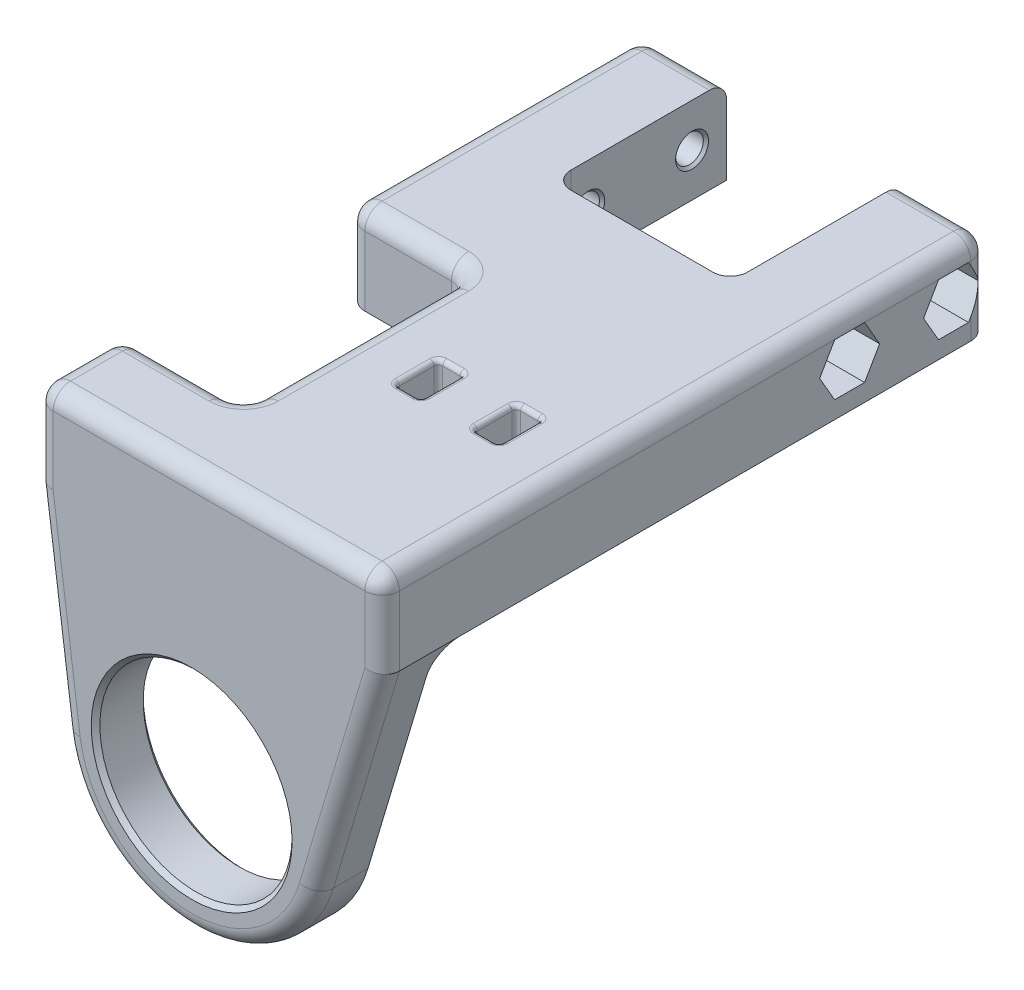
SolidWorks part; units mm, degrees
ref_plane "Top Plane" through (0, 0, 0) normal (0, 0, 1) x (1, 0, 0)
ref_plane "Right Plane" through (0, 0, 0) normal (0, 1, 0) x (1, 0, 0)
ref_plane "Front Plane" through (0, 0, 0) normal (1, 0, 0) x (0, 0, -1)
sketch "Sketch1" plane through (0, 0, 0) normal (0, 0, 1) x (1, 0, 0)
  line L0 (0, 0) -> (0, 31.25) construction
  line L1 (22, 31.25) -> (22, 21.25)
  line L2 (-18, 31.25) -> (22, 31.25)
  line L3 (-18, 31.25) -> (-18, 21.25)
  line L4 (22, 21.25) -> (14.3729, -4.2919)
  line L5 (-18, 21.25) -> (-14.8656, -2.0038)
  line L6 (-18, 21.25) -> (22, 21.25) construction
  arc A0 (-14.8656, -2.0038) -> (14.3729, -4.2919) centre (0, 0) ccw construction
  circle A1 centre (0, 0) radius 11 construction
  circle A2 centre (0, 0) radius 4 construction
  arc A3 (-14.8656, -2.0038) -> (14.3729, -4.2919) centre (0, 0) ccw
  dimension "D1" = 30
  dimension "D2" = 22
  dimension "D3" = 8
  dimension "D6" = 10
  dimension "D4" = 21.25
  dimension "D5" = 40
  dimension "D7" = 18
extrude "Boss-Extrude1" add sketch "Sketch1" along normal blind 6
sketch "Sketch2" plane through (0, 0, 6) normal (0, 0, 1) x (1, 0, 0)
  circle A2 centre (0, 0) radius 11.1
  circle A3 centre (0, 0) radius 11.1
  dimension "D1" = 0.1
extrude "Cut-Extrude1" cut sketch "Sketch2" against normal through all
sketch "Sketch3" plane through (0, 0, 0) normal (0, 0, -1) x (-1, 0, 0)
  line L0 (18, 31.25) -> (-22, 31.25) construction
  line L1 (-22, 31.25) -> (-12, 31.25) construction
  line L2 (-22, 31.25) -> (-22, 21.25) construction
  line L3 (-22, 21.25) -> (-12, 21.25) construction
  line L4 (-12, 31.25) -> (-12, 21.25) construction
  line L5 (8, 31.25) -> (18, 31.25) construction
  line L6 (8, 31.25) -> (8, 21.25) construction
  line L7 (8, 21.25) -> (18, 21.25) construction
  line L8 (18, 31.25) -> (18, 21.25) construction
  line L9 (-12, 26.25) -> (8, 26.25) construction
  line L11 (-2, 26.25) -> (-2, 31.25) construction
  line L13 (-22, 31.25) -> (18, 31.25)
  line L14 (-22, 31.25) -> (-22, 21.25)
  line L15 (-22, 21.25) -> (18, 21.25)
  line L16 (18, 31.25) -> (18, 21.25)
  point P12 (-2, 26.25)
  dimension "D1" = 20
extrude "Boss-Extrude2" add sketch "Sketch3" along normal blind 44
sketch "Sketch4" plane through (0, 0, -44) normal (0, 0, -1) x (-1, 0, 0)
  line L0 (-22, 21.25) -> (18, 21.25) construction
  line L1 (-22, 31.25) -> (-12.2, 31.25)
  line L2 (-22, 31.25) -> (-22, 21.25)
  line L3 (-22, 21.25) -> (-12.2, 21.25)
  line L4 (-12.2, 31.25) -> (-12.2, 21.25)
  line L5 (8.2, 31.25) -> (18, 31.25)
  line L6 (8.2, 31.25) -> (8.2, 21.25)
  line L7 (8.2, 21.25) -> (18, 21.25)
  line L8 (18, 31.25) -> (18, 21.25)
  line L9 (-12, 31.25) -> (-12, 21.25) construction
  line L10 (8, 31.25) -> (8, 21.25) construction
  line L11 (18, 31.25) -> (-22, 31.25) construction
  dimension "D1" = 0.2
  dimension "D2" = 0.2
extrude "Boss-Extrude3" add sketch "Sketch4" along normal blind 20
fillet "Fillet1" radius 3 1 edges at (2, 21.25, 0)
sketch "Sketch5" plane through (12.2, 0, 0) normal (-1, 0, 0) x (0, 0, 1)
  line L0 (-64, 26.25) -> (-44, 26.25) construction
  line L1 (-64, 21.25) -> (-64, 31.25) construction
  line L2 (-44, 21.25) -> (-44, 31.25) construction
  line L3 (-54, 31.25) -> (-54, 26.25) construction
  line L4 (-64, 31.25) -> (-44, 31.25) construction
  circle A0 centre (-60, 26.25) radius 1.75
  circle A1 centre (-48, 26.25) radius 1.75
  dimension "D1" = 3.5
  dimension "D2" = 12
hole_wizard "CBORE for M3 Hex Socket Head Cap Screw1" positions "Sketch6" profile "Sketch7" counterbore size "M3" standard "ISO" end condition through all
sketch "Sketch6" plane through (-18, 0, 0) normal (-1, 0, 0) x (0, 0, 1)
  point P0 (-60, 26.25)
  point P3 (-48, 26.25)
sketch "Sketch7" plane through (-18, 26.25, -60) normal (0, 1, 0) x (0, 0, 1)
  line L0 (0, 0) -> (0, 40)
  line L1 (0, 40) -> (1.6, 40)
  line L3 (1.6, 40) -> (1.6, 3.4)
  line L4 (1.6, 3.4) -> (3.25, 3.4)
  line L5 (3.25, 3.4) -> (3.25, 0)
  line L7 (3.25, 0) -> (0, 0)
  line L11 (0, -6.35) -> (0, 107.95) construction
  dimension "Thru Hole Dia." = 3.2
  dimension "Thru Hole Depth" = 40
  dimension "C'Bore Dia." = 6.5
  dimension "C'Bore Depth" = 3.4
sketch "Sketch8" plane through (22, 0, 0) normal (1, 0, 0) x (0, 0, -1)
  line L1 (49.7321, 29.25) -> (46.2679, 29.25)
  line L2 (46.2679, 29.25) -> (44.5359, 26.25)
  line L3 (44.5359, 26.25) -> (46.2679, 23.25)
  line L4 (46.2679, 23.25) -> (49.7321, 23.25)
  line L5 (49.7321, 23.25) -> (51.4641, 26.25)
  line L6 (51.4641, 26.25) -> (49.7321, 29.25)
  line L7 (58.2679, 29.25) -> (56.5359, 26.25)
  line L8 (56.5359, 26.25) -> (58.2679, 23.25)
  line L9 (58.2679, 23.25) -> (61.7321, 23.25)
  line L10 (61.7321, 23.25) -> (63.4641, 26.25)
  line L11 (63.4641, 26.25) -> (61.7321, 29.25)
  line L12 (61.7321, 29.25) -> (58.2679, 29.25)
  circle A0 centre (48, 26.25) radius 3 construction
  circle A1 centre (60, 26.25) radius 3 construction
  dimension "D1" = 6
extrude "Cut-Extrude3" cut sketch "Sketch8" against normal offset from surface (5.8 mm away) 4 up to face at (12.2, 27.85, -60)
sketch "Sketch9" plane through (0, 31.25, 0) normal (0, 1, 0) x (1, 0, 0)
  line L0 (-18, -6) -> (-18, 64) construction
  line L1 (-18, 30) -> (-4, 30)
  line L2 (-18, 30) -> (-18, 4)
  line L3 (-18, 4) -> (-4, 4)
  line L4 (-4, 30) -> (-4, 4)
  line L5 (22, -6) -> (-18, -6) construction
  dimension "D1" = 36
  dimension "D2" = 10
  dimension "D3" = 14
extrude "Cut-Extrude4" cut sketch "Sketch9" against normal through all
sketch "Sketch10" plane through (0, 31.25, 0) normal (0, 1, 0) x (1, 0, 0)
  line L0 (9, 23.4892) -> (9, 10.5108) construction
  line L1 (3, 19.5) -> (6, 19.5)
  line L2 (3, 19.5) -> (3, 14.5)
  line L3 (3, 14.5) -> (6, 14.5)
  line L4 (6, 19.5) -> (6, 14.5)
  line L5 (12, 19.5) -> (12, 14.5)
  line L6 (15, 14.5) -> (12, 14.5)
  line L7 (15, 19.5) -> (15, 14.5)
  line L8 (15, 19.5) -> (12, 19.5)
  line L9 (3, 17) -> (15, 17) construction
  line L10 (-4, 17) -> (9, 17) construction
  line L11 (-4, 4) -> (-4, 30) construction
  line L12 (-4, 10.5108) -> (22, 10.5108) construction
  line L13 (22, -6) -> (22, 64) construction
  point P10 (9, 17)
  dimension "D1" = 3
  dimension "D2" = 5
  dimension "D3" = 6
fillet "Fillet2" radius 2 2 edges at (-4, 26.25, -4) (-4, 26.25, -30)
fillet "Fillet3" radius 2 2 edges at (12.2, 26.25, -44) (-8.2, 26.25, -44)
fillet "Fillet4" radius 2 9 edges at (-16.4328, 9.6231, 6) (-1.1703, -14.9543, 6) (18.1864, 8.479, 6) (-18, 26.25, 6) (22, 26.25, 6) (-18, 26.25, -4) (-18, 26.25, -30) (22, 26.25, -64) (-18, 26.25, -64)
fillet "Fillet5" radius 2 17 edges at (-12.1, 31.25, -64) (-17.4142, 31.25, -63.4142) (-18, 31.25, -47) (-17.4142, 31.25, -30.5858) (-11, 31.25, -30) (-4.5858, 31.25, -29.4142) (-4, 31.25, -17) (-4.5858, 31.25, -4.5858) (-11, 31.25, -4) (-17.4142, 31.25, -3.4142) (-18, 31.25, 1) (-17.4142, 31.25, 5.4142) (2, 31.25, 6) (21.4142, 31.25, 5.4142) (16.1, 31.25, -64) (21.4142, 31.25, -63.4142) (22, 31.25, -29)
chamfer "Chamfer1" distance 0.5 angle 45 2 edges at (11.1, 0, 6) (11.1, 0, 0)
extrude "Cut-Extrude5" cut sketch "Sketch10" against normal up to next
fillet "Fillet6" radius 0.5 24 edges at (13.5, 21.25, -14.5) (13.5, 31.25, -14.5) (13.5, 31.25, -19.5) (13.5, 21.25, -19.5) (4.5, 21.25, -14.5) (4.5, 31.25, -14.5) (4.5, 31.25, -19.5) (4.5, 21.25, -19.5) (15, 26.25, -19.5) (15, 31.25, -17) (15, 26.25, -14.5) (15, 21.25, -17) (12, 26.25, -14.5) (12, 31.25, -17) (12, 26.25, -19.5) (12, 21.25, -17) (6, 26.25, -19.5) (6, 31.25, -17) (6, 26.25, -14.5) (6, 21.25, -17) (3, 26.25, -14.5) (3, 31.25, -17) (3, 26.25, -19.5) (3, 21.25, -17)
chamfer "Chamfer2" distance 0.3 angle 45 6 edges at (-14.6, 26.25, -46.4) (-14.6, 26.25, -58.4) (-8.2, 26.25, -46.4) (-8.2, 26.25, -58.4) (12.2, 27.85, -48) (12.2, 27.85, -60)
